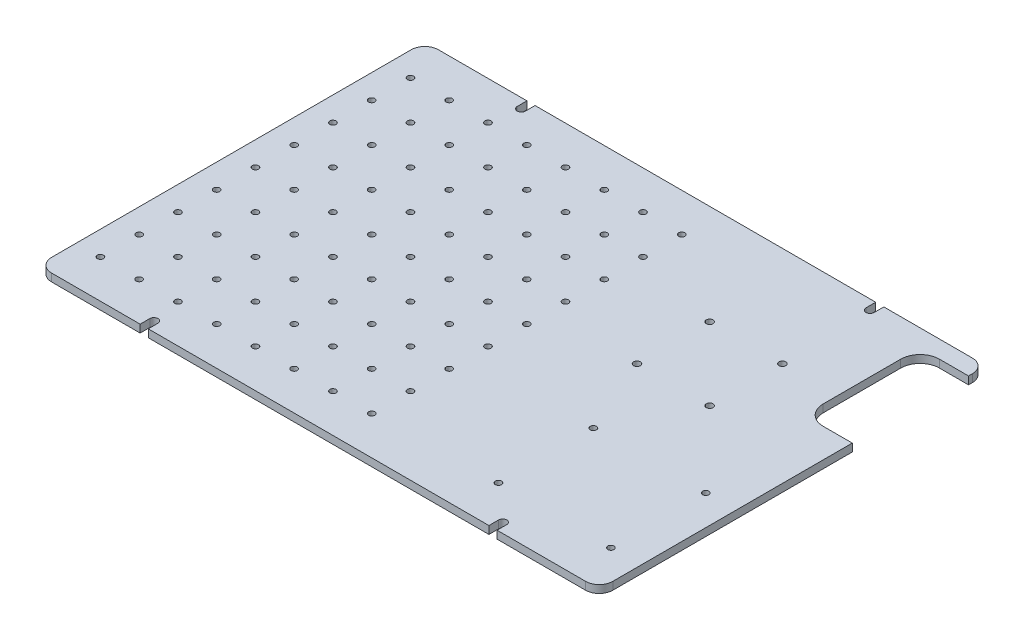
SolidWorks part; units mm, degrees
ref_plane "Front Plane" through (0, 0, 0) normal (0, 0, 1) x (1, 0, 0)
ref_plane "Top Plane" through (0, 0, 0) normal (0, 1, 0) x (1, 0, 0)
ref_plane "Right Plane" through (0, 0, 0) normal (1, 0, 0) x (0, 0, -1)
sketch "Sketch1" plane through (0, 0, 0) normal (0, 1, 0) x (1, 0, 0)
  line L1 (-144.8, 99.8) -> (144.8, 99.8)
  line L2 (-144.8, 99.8) -> (-144.8, -99.8)
  line L3 (-144.8, -99.8) -> (144.8, -99.8)
  line L4 (144.8, 99.8) -> (144.8, -99.8)
  line L5 (-144.8, 99.8) -> (144.8, -99.8) construction
  line L6 (-144.8, -99.8) -> (144.8, 99.8) construction
  point P0 (0, 0)
  dimension "D1" = 289.6
  dimension "D2" = 199.6
extrude "Boss-Extrude1" add sketch "Sketch1" along normal blind 4
sketch "Sketch2" plane through (0, 4, 0) normal (0, 1, 0) x (1, 0, 0)
  line L0 (-90, 104.8) -> (-90, 94.8) construction
  line L1 (-87.9, 104.8) -> (-87.9, 94.8)
  line L2 (-92.1, 104.8) -> (-92.1, 94.8)
  line L3 (90, 104.8) -> (90, 94.8) construction
  line L4 (92.1, 104.8) -> (92.1, 94.8)
  line L5 (87.9, 104.8) -> (87.9, 94.8)
  line L6 (144.8, 99.8) -> (-144.8, 99.8) construction
  arc A0 (-87.9, 104.8) -> (-92.1, 104.8) centre (-90, 104.8) ccw
  arc A1 (-92.1, 94.8) -> (-87.9, 94.8) centre (-90, 94.8) ccw
  arc A2 (92.1, 104.8) -> (87.9, 104.8) centre (90, 104.8) ccw
  arc A3 (87.9, 94.8) -> (92.1, 94.8) centre (90, 94.8) ccw
  point P2 (-90, 99.8)
  point P7 (90, 99.8)
  dimension "D1" = 4.2
  dimension "D2" = 180
  dimension "D3" = 10
  dimension "D4" = 90
extrude "Cut-Extrude1" cut sketch "Sketch2" against normal through all
mirror "Mirror1" about plane through (0, 0, 0) normal (0, 0, 1) of "Cut-Extrude1"
fillet "Fillet1" radius 7 4 edges at (144.8, 2, -99.8) (144.8, 2, 99.8) (-144.8, 2, 99.8) (-144.8, 2, -99.8)
sketch "Sketch3" plane through (0, 4, 0) normal (0, 1, 0) x (1, 0, 0)
  line L0 (144.8, -92.8) -> (144.8, 92.8) construction
  line L1 (119.8, 90.8) -> (144.8, 90.8)
  line L2 (119.8, 90.8) -> (119.8, 30.8)
  line L3 (119.8, 30.8) -> (144.8, 30.8)
  line L4 (144.8, 90.8) -> (144.8, 30.8)
  line L6 (137.8, 99.8) -> (92.1, 99.8) construction
  dimension "D1" = 25
  dimension "D2" = 60
  dimension "D3" = 9
extrude "Cut-Extrude2" cut sketch "Sketch3" against normal through all
fillet "Fillet2" radius 10 2 edges at (119.8, 2, -30.8) (119.8, 2, -90.8)
sketch "Sketch4" plane through (0, 4, 0) normal (0, 1, 0) x (1, 0, 0)
  line L1 (144.8, -92.8) -> (144.8, 30.8) construction
  line L2 (-87.9, -99.8) -> (87.9, -99.8) construction
  line B0 (132.8, -81.8) -> (132.8, -25.8) construction
  line B1 (45.428, -81.8) -> (132.8, -81.8) construction
  circle B2 centre (129.3, -78.3) radius 1.6
  circle B3 centre (71.3, -78.3) radius 1.6
  circle B4 centre (129.3, -29.3) radius 1.6
  circle B5 centre (71.3, -29.3) radius 1.6
  dimension "D1" = 12
  dimension "D2" = 18
sketch_block_instance "Raspberry_Pi_3-1"
sketch_block "Raspberry_Pi_3" parameters "D11"=3.2, "D1"=87.372, "D2"=56, "D3"=3.5, "D4"=3.5, "D5"=3.5, "D6"=3.5, "D7"=3.5, "D8"=3.5, "D9"=58, "D10"=58
extrude "Cut-Extrude3" cut sketch "Sketch4" against normal through all
sketch "Sketch5" plane through (0, 4, 0) normal (0, 1, 0) x (1, 0, 0)
  circle A0 centre (91.3, 10.7) radius 1.75
  circle A1 centre (91.3, 48.2) radius 1.75
  circle A2 centre (53.8, 48.2) radius 1.75
  circle A3 centre (53.8, 10.7) radius 1.75
  circle A4 centre (71.3, -29.3) radius 1.6 construction
  point P8 (0, 0)
  point P9 (0, 0)
  point P10 (0, 0)
  point P11 (0, 0)
  point P12 (0, 0)
  point P13 (15.1828, -28.2401)
  point P14 (23.4461, -45.7677)
  point P15 (16.6185, -58.0103)
  point P16 (90.5449, 36.3989)
  dimension "D3" = 3.5
  dimension "D1" = 37.5
  dimension "D2" = 37.5
  dimension "D4" = 40
  dimension "D5" = 20
extrude "Cut-Extrude4" cut sketch "Sketch5" against normal through all
sketch "Sketch6" plane through (0, 4, 0) normal (0, 1, 0) x (1, 0, 0)
  line L1 (87.9, 99.8) -> (-87.9, 99.8) construction
  line L4 (-144.8, 92.8) -> (-144.8, -92.8) construction
  circle A0 centre (7.6, 80) radius 1.59
  circle A1 centre (-12.4, 80) radius 1.59
  circle A2 centre (-32.4, 80) radius 1.59
  circle A3 centre (-52.4, 80) radius 1.59
  circle A4 centre (-72.4, 80) radius 1.59
  circle A5 centre (-92.4, 80) radius 1.59
  circle A6 centre (-112.4, 80) radius 1.59
  circle A7 centre (-12.4, 60) radius 1.59
  circle A8 centre (-32.4, 60) radius 1.59
  circle A9 centre (-52.4, 60) radius 1.59
  circle A10 centre (-72.4, 60) radius 1.59
  circle A11 centre (-92.4, 60) radius 1.59
  circle A12 centre (-112.4, 60) radius 1.59
  circle A13 centre (-12.4, 40) radius 1.59
  circle A14 centre (-32.4, 40) radius 1.59
  circle A15 centre (-52.4, 40) radius 1.59
  circle A16 centre (-72.4, 40) radius 1.59
  circle A17 centre (-92.4, 40) radius 1.59
  circle A18 centre (-112.4, 40) radius 1.59
  circle A19 centre (-12.4, 20) radius 1.59
  circle A20 centre (-32.4, 20) radius 1.59
  circle A21 centre (-52.4, 20) radius 1.59
  circle A22 centre (-72.4, 20) radius 1.59
  circle A23 centre (-92.4, 20) radius 1.59
  circle A24 centre (-112.4, 20) radius 1.59
  circle A25 centre (-12.4, 0) radius 1.59
  circle A26 centre (-32.4, 0) radius 1.59
  circle A27 centre (-52.4, 0) radius 1.59
  circle A28 centre (-72.4, 0) radius 1.59
  circle A29 centre (-92.4, 0) radius 1.59
  circle A30 centre (-112.4, 0) radius 1.59
  circle A31 centre (-12.4, -20) radius 1.59
  circle A32 centre (-32.4, -20) radius 1.59
  circle A33 centre (-52.4, -20) radius 1.59
  circle A34 centre (-72.4, -20) radius 1.59
  circle A35 centre (-92.4, -20) radius 1.59
  circle A36 centre (-112.4, -20) radius 1.59
  circle A37 centre (-12.4, -40) radius 1.59
  circle A38 centre (-32.4, -40) radius 1.59
  circle A39 centre (-52.4, -40) radius 1.59
  circle A40 centre (-72.4, -40) radius 1.59
  circle A41 centre (-92.4, -40) radius 1.59
  circle A42 centre (-112.4, -40) radius 1.59
  circle A43 centre (-12.4, -60) radius 1.59
  circle A44 centre (-32.4, -60) radius 1.59
  circle A45 centre (-52.4, -60) radius 1.59
  circle A46 centre (-72.4, -60) radius 1.59
  circle A47 centre (-92.4, -60) radius 1.59
  circle A48 centre (-112.4, -60) radius 1.59
  circle A49 centre (-12.4, -80) radius 1.59
  circle A50 centre (-32.4, -80) radius 1.59
  circle A51 centre (-52.4, -80) radius 1.59
  circle A52 centre (-72.4, -80) radius 1.59
  circle A53 centre (-92.4, -80) radius 1.59
  circle A54 centre (-112.4, -80) radius 1.59
  circle A55 centre (7.6, 60) radius 1.59
  circle A56 centre (7.6, 40) radius 1.59
  circle A57 centre (7.6, 20) radius 1.59
  circle A58 centre (7.6, 0) radius 1.59
  circle A59 centre (7.6, -20) radius 1.59
  circle A60 centre (7.6, -40) radius 1.59
  circle A61 centre (7.6, -60) radius 1.59
  circle A62 centre (7.6, -80) radius 1.59
  circle A63 centre (-132.4, 80) radius 1.59
  circle A64 centre (-132.4, 60) radius 1.59
  circle A65 centre (-132.4, 40) radius 1.59
  circle A66 centre (-132.4, 20) radius 1.59
  circle A67 centre (-132.4, 0) radius 1.59
  circle A68 centre (-132.4, -20) radius 1.59
  circle A69 centre (-132.4, -40) radius 1.59
  circle A70 centre (-132.4, -60) radius 1.59
  circle A71 centre (-132.4, -80) radius 1.59
  point P8 (-5.6746, 80)
  dimension "D2" = 3.18
  dimension "D1" = 19.8
  dimension "D5" = 92.4
  dimension "D3" = 8
  dimension "D4" = 9
extrude "Cut-Extrude5" cut sketch "Sketch6" against normal through all
